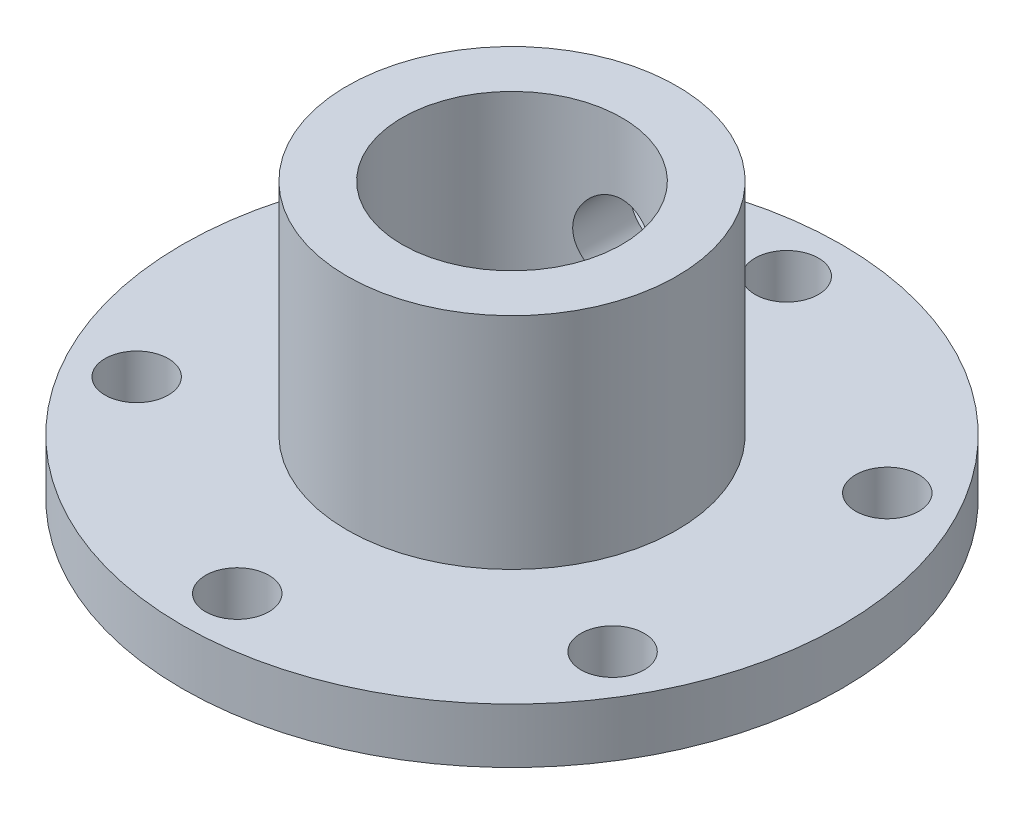
SolidWorks part; units mm, degrees
ref_plane "Front Plane" through (0, 0, 0) normal (0, 0, 1) x (1, 0, 0)
ref_plane "Top Plane" through (0, 0, 0) normal (0, 1, 0) x (1, 0, 0)
ref_plane "Right Plane" through (0, 0, 0) normal (1, 0, 0) x (0, 0, -1)
sketch "Sketch1" plane through (0, 0, 0) normal (0, 1, 0) x (1, 0, 0)
  circle A0 centre (0, 0) radius 19.05
  dimension "D1" = 38.1
extrude "Boss-Extrude1" add sketch "Sketch1" along normal blind 3.175
sketch "Sketch2" plane through (0, 3.175, 0) normal (0, 1, 0) x (1, 0, 0)
  circle A0 centre (0, 0) radius 9.525
  circle A1 centre (0, 0) radius 6.35
  dimension "D1" = 19.05
  dimension "D2" = 12.7
extrude "Boss-Extrude2" add sketch "Sketch2" along normal blind 12.7
hole_wizard "#27 (0.144) Diameter Hole1" positions "Sketch4" profile "Sketch3" hole size "#27" standard "Ansi Inch"
sketch "Sketch4" plane through (0, 3.175, 0) normal (0, 1, 0) x (-1, 0, 0)
  point P0 (0, 15.875)
  dimension "D1" = 15.875
sketch "Sketch3" plane through (0, 3.175, 15.875) normal (1, 0, 0) x (0, 0, 1)
  line L0 (0, 0) -> (0, 26.4989)
  line L1 (0, 26.4989) -> (1.8288, 25.4)
  line L2 (1.8288, 25.4) -> (1.8288, 0)
  line L5 (1.8288, 0) -> (0, 0)
  line L10 (0, 26.4989) -> (-1.8288, 25.4) construction
  line L11 (0, -6.35) -> (0, 107.95) construction
  dimension "Hole Dia." = 3.6576
  dimension "Hole Depth" = 25.4
  dimension "Drill Angle" = 118
ref_axis "Axis1" through (0, 15.875, 0) along (0, -1, 0)
pattern_circular "CirPattern1" count 6 over 360 about axis through (0, 15.875, 0) along (0, -1, 0) of "#27 (0.144) Diameter Hole1"
sketch "Sketch5" plane through (0, 0, 0) normal (0, 0, 1) x (1, 0, 0)
  line L0 (0, 15.875) -> (0, 3.175) construction
  circle A0 centre (0, 9.4089) radius 2.3813
  dimension "D1" = 4.7625
extrude "Cut-Extrude1" cut sketch "Sketch5" against normal blind 12.7
